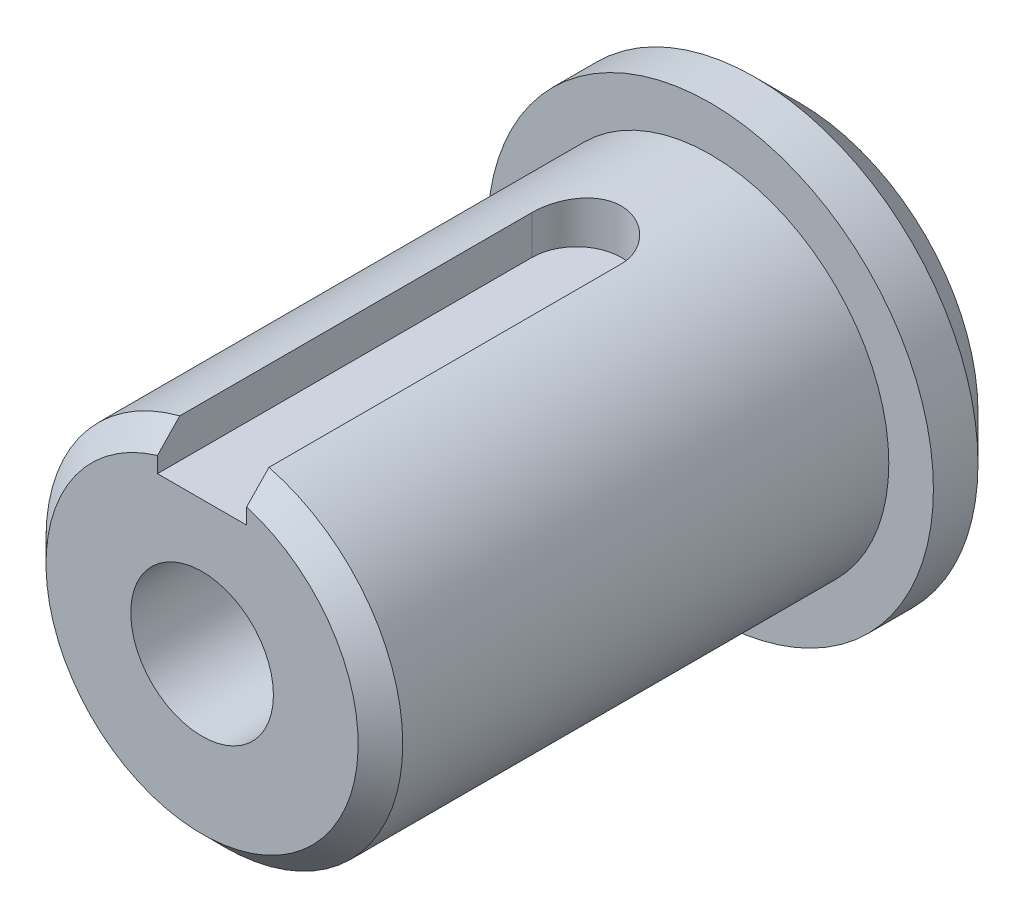
SolidWorks part; units mm, degrees
material "Plain Carbon Steel"
ref_plane "Front" through (0, 0, 0) normal (0, 0, 1) x (1, 0, 0)
ref_plane "Top" through (0, 0, 0) normal (0, 1, 0) x (1, 0, 0)
ref_plane "Right" through (0, 0, 0) normal (1, 0, 0) x (0, 0, -1)
sketch "Sketch1" plane through (0, 0, 0) normal (1, 0, 0) x (0, 0, -1)
  line L0 (0, 1.6) -> (0, 4)
  line L1 (0, 4) -> (-1, 5)
  line L2 (-1, 5) -> (-2, 5)
  line L3 (-2, 5) -> (-2, 4)
  line L4 (-2, 4) -> (-12.9, 4)
  line L5 (-12.9, 4) -> (-13.4, 3.5)
  line L6 (-13.4, 3.5) -> (-13.4, 1.6)
  line L7 (-13.4, 1.6) -> (0, 1.6)
  line L10 (0, 0) -> (3.2083, 0) construction
  point P11 (0, 0)
  dimension "D1" = 3.2
  dimension "D3" = 8
  dimension "D4" = 10
  dimension "D5" = 8
  dimension "D6" = 0.5
  dimension "D7" = 45
  dimension "D8" = 2
  dimension "D9" = 45
  dimension "D10" = 11.4
revolve "Revolve1" add sketch "Sketch1" angle 360 about L10
ref_plane "Plane1" through (0, 4, 0) normal (0, 1, 0) x (1, 0, 0)
sketch "Sketch2" plane through (0, 4, 0) normal (0, 1, 0) x (1, 0, 0)
  line L0 (0, -13.4) -> (0, -5) construction
  line L1 (-1, -13.4) -> (-1, -5)
  line L2 (1, -13.4) -> (1, -5)
  line L3 (-3.5, -13.4) -> (3.5, -13.4) construction
  arc A0 (-1, -13.4) -> (1, -13.4) centre (0, -13.4) ccw
  arc A1 (1, -5) -> (-1, -5) centre (0, -5) ccw
  point P3 (0, -9.2)
  dimension "D2" = 9.4
  dimension "D1" = 2
extrude "Cut-Extrude1" cut sketch "Sketch2" against normal blind 1
